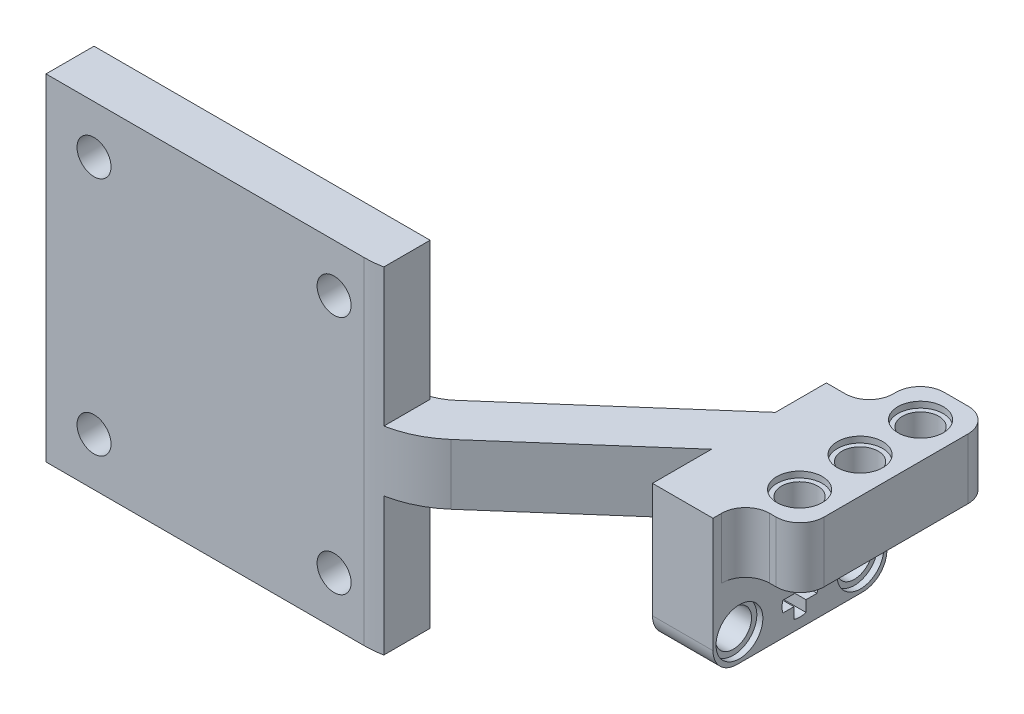
SolidWorks part; units mm, degrees
ref_plane "Front Plane" through (0, 0, 0) normal (0, 0, 1) x (1, 0, 0)
ref_plane "Top Plane" through (0, 0, 0) normal (0, 1, 0) x (1, 0, 0)
ref_plane "Right Plane" through (0, 0, 0) normal (1, 0, 0) x (0, 0, -1)
sketch "Sketch6" plane through (0, 0, 0) normal (0, 1, 0) x (1, 0, 0)
  line L1 (-4.7625, 12.7) -> (4.7625, 12.7)
  line L2 (-4.7625, 12.7) -> (-4.7625, -12.7)
  line L3 (-4.7625, -12.7) -> (4.7625, -12.7)
  line L4 (4.7625, 12.7) -> (4.7625, -12.7)
  line L5 (-4.7625, 12.7) -> (4.7625, -12.7) construction
  line L6 (-4.7625, -12.7) -> (4.7625, 12.7) construction
  point P0 (0, 0)
  dimension "D1" = 9.525
  dimension "D2" = 25.4
extrude "Boss-Extrude1" add sketch "Sketch6" against normal blind 8
sketch "Sketch16" plane through (0, 0, 0) normal (0, -1, 0) x (1, 0, 0)
  line L1 (-2.4423, -5.9876) -> (-10.4423, -5.9876)
  line L2 (-2.4423, -5.9876) -> (-2.4423, 17.0124)
  line L3 (-2.4423, 17.0124) -> (-10.4423, 17.0124)
  line L4 (-10.4423, -5.9876) -> (-10.4423, 17.0124)
  line L5 (-2.4423, -5.9876) -> (-10.4423, 17.0124) construction
  line L6 (-2.4423, 17.0124) -> (-10.4423, -5.9876) construction
  line L7 (-4.7625, -12.7) -> (-4.7625, 12.7) construction
  point P0 (-6.4423, 5.5124)
  point P12 (-4.7625, 0)
  dimension "D1" = 6.4423
  dimension "D2" = 5.5124
  dimension "D3" = 8
  dimension "D4" = 23
extrude "Boss-Extrude6" add sketch "Sketch16" along normal up to surface (8 mm away) up to face at (0, -8, 0)
sketch "Sketch7" plane through (0, 0, 0) normal (0, 1, 0) x (1, 0, 0)
  circle A0 centre (0, 8) radius 2.4
  circle A1 centre (0, 0) radius 2.4
  circle A2 centre (0, -8) radius 2.4
  circle A3 centre (0, 8) radius 3
  circle A4 centre (0, 0) radius 3
  circle A5 centre (0, -8) radius 3
  dimension "D3" = 4.8
  dimension "D1" = 8
  dimension "D2" = 8
  dimension "D4" = 0.6
extrude "Cut-Extrude1" cut sketch "Sketch7" against normal blind 0.8
extrude "Cut-Extrude2" cut sketch "Sketch7<3>" against normal blind 7.2 contours A0 | A1 | A2 region at (0, 0, -8) region at (0, 0, 0) region at (0, 0, 8)
sketch "Sketch7<3>" plane through (0, 0, 0) normal (0, 1, 0) x (1, 0, 0) same geometry as "Sketch7"
sketch "Sketch9" plane through (0, -7.2, -7.2) normal (0, 1, 0) x (1, 0, 0)
  circle A0 centre (0, 0.8) radius 2.4
  circle A1 centre (0, -7.2) radius 2.4
  circle A2 centre (0, -15.2) radius 2.4
  circle A3 centre (0, 0.8) radius 3
  circle A4 centre (0, -7.2) radius 3
  circle A5 centre (0, -15.2) radius 3
  dimension "D3" = 4.8
  dimension "D1" = 8
  dimension "D2" = 8
  dimension "D4" = 0.6
extrude "Cut-Extrude4" cut sketch "Sketch9" against normal blind 0.8 contours A3 | A4 | A5
ref_plane "Plane4" through (0, 0, 28.448) normal (0, 0, 1) x (1, 0, 0)
sketch "Sketch10" plane through (0, -8, 0) normal (0, -1, 0) x (-1, 0, 0)
  line L1 (4.7625, 4.2239) -> (34.7625, -22.098)
  line L2 (4.7625, 4.2239) -> (4.7625, -4.2239) construction
  line L3 (34.7625, -22.098) -> (60.1625, -22.098)
  line L4 (60.1625, -22.098) -> (60.1625, -28.448)
  line L5 (-57.9984, -28.448) -> (57.9984, -28.448) construction
  line L8 (4.7625, -4.2239) -> (32.3717, -28.448)
  line L10 (4.7625, 4.2239) -> (4.7625, -4.2239)
  line L14 (4.7625, 12.7) -> (4.7625, 5.9876) construction
  line L18 (32.3717, -28.448) -> (60.1625, -28.448)
  point P2 (4.7625, 0)
  dimension "D1" = 30
  dimension "D2" = 6.35
  dimension "D3" = 25.4
  dimension "D4" = 6.35
extrude "Boss-Extrude3" add sketch "Sketch10" against normal up to surface (8 mm away) up to face at (0, 0, -5)
fillet "Fillet1" radius 3.175 2 edges at (-4.7625, -4, -5.9876) (-2.4423, -4, 12.7)
fillet "Fillet3" radius 3.175 3 edges at (4.7625, -4, -12.7) (4.7625, -4, 12.7) (-4.7625, -4, -12.7)
sketch "Sketch18" plane through (0, 0, 0) normal (0, 1, 0) x (1, 0, 0)
  line L0 (-57.9984, -28.448) -> (57.9984, -28.448) construction
  line L1 (-79.2125, -22.098) -> (-34.7625, -22.098)
  line L2 (-79.2125, -22.098) -> (-79.2125, -28.448)
  line L3 (-79.2125, -28.448) -> (-34.7625, -28.448)
  line L4 (-34.7625, -22.098) -> (-34.7625, -28.448)
  dimension "D1" = 44.45
extrude "Boss-Extrude7" add sketch "Sketch18" along normal blind 18.225 and the other way blind 26.225
fillet "Fillet6" radius 12.7 1 edges at (-32.3717, -4, 28.448)
fillet "Fillet7" radius 6.35 1 edges at (-34.7625, -4, 22.098)
sketch "Sketch11" plane through (0, -8, 0) normal (0, -1, 0) x (-1, 0, 0)
  line L1 (10.4422, -17.0124) -> (2.4422, -17.0124)
  line L2 (10.4422, -17.0124) -> (10.4422, 5.9876)
  line L3 (10.4422, 5.9876) -> (2.4422, 5.9876)
  line L4 (2.4422, -17.0124) -> (2.4422, 5.9876)
  line L5 (10.4422, -17.0124) -> (2.4422, 5.9876) construction
  line L6 (10.4422, 5.9876) -> (2.4422, -17.0124) construction
  point P0 (6.4422, -5.5124)
  dimension "D1" = 6.4422
  dimension "D3" = 8
  dimension "D4" = 23
  dimension "D5" = 5.5124
extrude "Boss-Extrude4" add sketch "Sketch11" along normal blind 6.7462 contours L4 L3 L2 L1
sketch "Sketch13" plane through (-2.4423, 0, 0) normal (1, 0, 0) x (0, 0, -1)
  line L0 (-17.0124, -14.7462) -> (5.9876, -14.7462) construction
  line L1 (-6.3124, -14.0148) -> (-6.3124, -12.5521)
  line L2 (-4.7124, -12.5521) -> (-4.7124, -14.0148)
  line L3 (-6.3124, -14.0148) -> (-4.7124, -14.0148) construction
  line L4 (-6.3124, -14.0148) -> (-6.3124, -15.4775) construction
  line L5 (-6.3124, -14.0148) -> (-7.7751, -14.0148)
  line L6 (-7.7751, -15.4775) -> (-6.3124, -15.4775)
  line L7 (-6.3124, -15.4775) -> (-6.3124, -16.9403)
  line L8 (-4.7124, -16.9403) -> (-4.7124, -15.4775)
  line L9 (-4.7124, -15.4775) -> (-3.2496, -15.4775)
  line L10 (-4.7124, -14.0148) -> (-3.2496, -14.0148)
  line L11 (-3.2496, -14.0148) -> (-5.9183, -14.0148)
  circle A0 centre (-5.5124, -14.7462) radius 2.5157 construction
  circle A1 centre (-13.5124, -14.7462) radius 3.1
  circle A2 centre (2.4876, -14.7462) radius 3.1
  circle A3 centre (-13.5124, -14.7462) radius 2.4
  circle A4 centre (2.4876, -14.7462) radius 2.4
  arc A5 (-6.3124, -12.5521) -> (-4.7124, -12.5521) centre (-5.5124, -15.0259) cw
  arc A6 (-7.7751, -14.0148) -> (-7.7751, -15.4775) centre (-5.2801, -14.7462) ccw
  arc A7 (-6.3124, -16.9403) -> (-4.7124, -16.9403) centre (-5.5124, -14.4664) ccw
  arc A8 (-3.2496, -14.0148) -> (-3.2496, -15.4775) centre (-5.7446, -14.7462) cw
  point P14 (-5.5124, -14.0148)
  point P16 (-6.3124, -14.7462)
  line M4 (-17.0124, -14.7462) -> (5.9876, -14.7462)
  dimension "D1" = 6.2
  dimension "D2" = 4.8
  dimension "D7" = 2.6
  dimension "D3" = 8
  dimension "D4" = 8
  dimension "D5" = 1.4627
  dimension "D6" = 1.6
sketch "Sketch14" plane through (0, -14.7462, 0) normal (0, -1, 0) x (-1, 0, 0)
  line L1 (10.4422, -17.0124) -> (2.4422, -17.0124)
  line L2 (10.4422, -17.0124) -> (10.4422, 5.9876)
  line L3 (10.4422, 5.9876) -> (2.4422, 5.9876)
  line L4 (2.4422, -17.0124) -> (2.4422, 5.9876)
extrude "Boss-Extrude5" add sketch "Sketch14" along normal blind 3.6 contours L2 L3 L4 L1
extrude "Cut-Extrude5" cut sketch "Sketch13" against normal blind 0.8 contours A3 A1 M4 | A3 A1 M4 | A8 A6 L6 L7 A7 L8 L9 M4 | A8 L10 L2 A5 L1 L5 A6 M4 | A4 A2 M4 | A4 A2 M4 region at (-2.4423, -11.7155, -2.4876) region at (-2.4423, -14.8155, 0.2624) region at (-2.4423, -17.7768, 13.5124) region at (-2.4423, -14.6768, 10.7624) region at (-2.4423, -13.9029, 5.5124) region at (-2.4423, -15.5895, 5.5124)
extrude "Cut-Extrude6" cut sketch "Sketch13<3>" against normal through all contours A8 A6 L6 L7 A7 L8 L9 M4 | A8 L10 L2 A5 L1 L5 A6 M4 | A4 M4 | A4 M4 | A3 region at (-2.4423, -13.9029, 5.5124) region at (-2.4423, -15.5895, 5.5124) region at (-2.4423, -15.7648, -2.4876) region at (-2.4423, -13.7276, -2.4876)
sketch "Sketch13<3>" plane through (-2.4423, 0, 0) normal (1, 0, 0) x (0, 0, -1) same geometry as "Sketch13"
ref_plane "Plane5" through (-6.4423, 0, 0) normal (1, 0, 0) x (0, 0, -1)
mirror "Mirror1" about plane through (-6.4423, 0, 0) normal (1, 0, 0) of "Cut-Extrude5"
hole_wizard "#8 Clearance Hole1" positions "Sketch19" profile "Sketch20" hole size "#8" standard "ANSI Inch" end condition through all
sketch "Sketch19" plane through (0, 0, 22.098) normal (0, 0, -1) x (-1, 0, 0)
  line L0 (34.7625, 0) -> (34.7625, 18.225) construction
  line L1 (34.7625, 18.225) -> (79.2125, 18.225) construction
  line L3 (34.7625, -26.225) -> (79.2125, -26.225) construction
  line L4 (79.2125, -26.225) -> (79.2125, 18.225) construction
  point P0 (72.8625, 11.875)
  point P2 (41.1125, 11.875)
  point P4 (41.1125, -19.875)
  point P6 (72.8625, -19.875)
  dimension "D1" = 6.35
  dimension "D2" = 6.35
  dimension "D3" = 6.35
  dimension "D4" = 6.35
sketch "Sketch20" plane through (-72.8625, 11.875, 22.098) normal (1, 0, 0) x (0, 1, 0)
  line L0 (0, 0) -> (0, 6.35)
  line L1 (0, 6.35) -> (2.2479, 6.35)
  line L2 (2.2479, 6.35) -> (2.2479, 0)
  line L5 (2.2479, 0) -> (0, 0)
  line L11 (0, -6.35) -> (0, 107.95) construction
  dimension "Thru Hole Dia." = 4.4958
  dimension "Thru Hole Depth" = 6.35
fillet "Fillet8" radius 3.175 2 edges at (-6.4422, -18.3462, 17.0124) (-6.4422, -18.3462, -5.9876)
